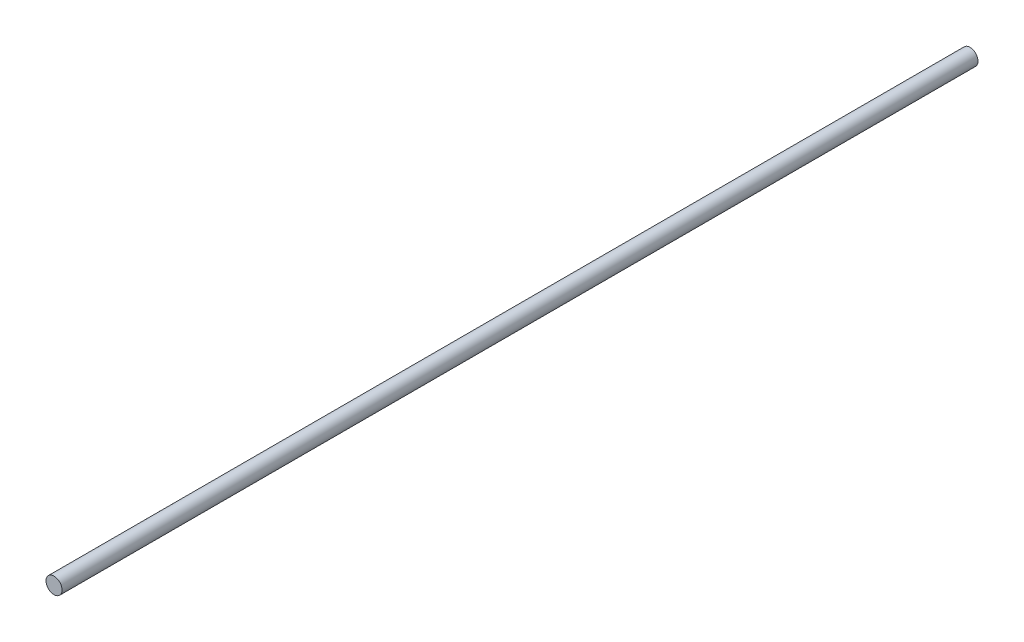
SolidWorks part; units mm, degrees
ref_plane "Plan de face" through (0, 0, 0) normal (0, 0, 1) x (1, 0, 0)
ref_plane "Plan de dessus" through (0, 0, 0) normal (0, 1, 0) x (1, 0, 0)
ref_plane "Plan de droite" through (0, 0, 0) normal (1, 0, 0) x (0, 0, -1)
sketch "Esquisse1" plane through (0, 0, 0) normal (0, 0, 1) x (1, 0, 0)
  circle A0 centre (0, 0) radius 2.5
  dimension "D1" = 5
extrude "Boss.-Extru.1" add sketch "Esquisse1" along normal blind 285
